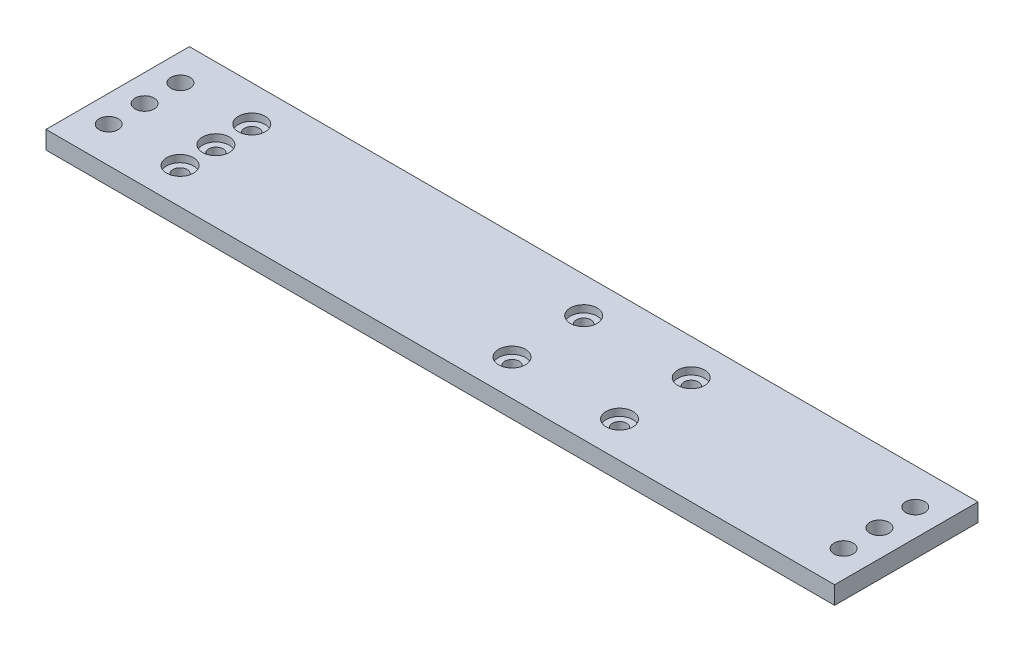
SolidWorks part; units mm, degrees
ref_plane "Front" through (0, 0, 0) normal (0, 0, 1) x (1, 0, 0)
ref_plane "Top" through (0, 0, 0) normal (0, 1, 0) x (1, 0, 0)
ref_plane "Right" through (0, 0, 0) normal (1, 0, 0) x (0, 0, -1)
sketch "Sketch1" plane through (0, 0, 0) normal (0, 1, 0) x (1, 0, 0)
  line L1 (-139.7, -25.4) -> (139.7, -25.4)
  line L2 (-139.7, -25.4) -> (-139.7, 25.4)
  line L3 (-139.7, 25.4) -> (139.7, 25.4)
  line L4 (139.7, -25.4) -> (139.7, 25.4)
  line L5 (-139.7, -25.4) -> (139.7, 25.4) construction
  line L6 (-139.7, 25.4) -> (139.7, -25.4) construction
  point P0 (0, 0)
  dimension "D1" = 50.8
  dimension "D2" = 279.4
extrude "Boss-Extrude1" add sketch "Sketch1" along normal blind 6.35
sketch "Sketch4" plane through (0, 6.35, 0) normal (0, 1, 0) x (1, 0, 0)
  line L0 (139.7, -25.4) -> (139.7, 25.4) construction
  line L1 (12.7, -12.7) -> (12.7, 12.7) construction
  line L2 (-139.7, 25.4) -> (-139.7, -25.4) construction
  line L3 (-104.902, 25.4) -> (-104.902, 12.7) construction
  line L4 (139.7, 25.4) -> (-139.7, 25.4) construction
  line L5 (-104.902, 12.7) -> (-104.902, 0) construction
  line L6 (-104.902, 0) -> (-104.902, -12.7) construction
  line L7 (-104.902, -12.7) -> (-104.902, -25.4) construction
  line L8 (-139.7, -25.4) -> (139.7, -25.4) construction
  point P0 (50.8, 12.7)
  point P2 (12.7, 12.7)
  point P4 (12.7, -12.7)
  point P6 (50.8, -12.7)
  point P23 (12.7, 0)
  point P25 (-104.902, 12.7)
  point P27 (-104.902, 0)
  point P29 (-104.902, -12.7)
  dimension "D1" = 38.1
  dimension "D2" = 88.9
  dimension "D3" = 25.4
  dimension "D4" = 34.798
hole_wizard "CBORE for #10 Socket Head Cap Screw1" positions "Sketch4" profile "Sketch3" counterbore size "#10" standard "ANSI Inch" end condition through all
sketch "Sketch3" plane through (50.8, 6.35, -12.7) normal (1, 0, 0) x (0, 0, 1)
  line L0 (0, 0) -> (0, 6.35)
  line L1 (0, 6.35) -> (2.5527, 6.35)
  line L3 (2.5527, 6.35) -> (2.5527, 2.54)
  line L4 (2.5527, 2.54) -> (4.7625, 2.54)
  line L5 (4.7625, 2.54) -> (4.7625, 0)
  line L7 (4.7625, 0) -> (0, 0)
  line L11 (0, -6.35) -> (0, 107.95) construction
  dimension "Thru Hole Dia." = 5.1054
  dimension "Thru Hole Depth" = 6.35
  dimension "C'Bore Dia." = 9.525
  dimension "C'Bore Depth" = 2.54
sketch "Sketch7" plane through (0, 0, 0) normal (0, -1, 0) x (1, 0, 0)
  line L5 (-130.175, 25.4) -> (-130.175, 12.7) construction
  line L6 (-139.7, 25.4) -> (139.7, 25.4) construction
  line L7 (-130.175, 12.7) -> (-130.175, 0) construction
  line L8 (-130.175, 0) -> (-130.175, -12.7) construction
  line L9 (-130.175, -12.7) -> (-130.175, -25.4) construction
  line L10 (139.7, -25.4) -> (-139.7, -25.4) construction
  line L12 (-139.7, -25.4) -> (-139.7, 25.4) construction
  line L13 (139.7, 25.4) -> (139.7, -25.4) construction
  point P0 (-130.175, 12.7)
  point P2 (-130.175, 0)
  point P4 (-130.175, -12.7)
  point P6 (130.175, 12.7)
  point P8 (130.175, 0)
  point P10 (130.175, -12.7)
  point P53 (0, 0)
  dimension "D1" = 9.525
  dimension "D2" = 9.525
hole_wizard "1/4 Clearance Hole1" positions "Sketch7" profile "Sketch6" hole size "1/4" standard "ANSI Inch" end condition through all
sketch "Sketch6" plane through (-130.175, 0, 12.7) normal (1, 0, 0) x (0, 0, -1)
  line L0 (0, 0) -> (0, 6.35)
  line L1 (0, 6.35) -> (3.3782, 6.35)
  line L2 (3.3782, 6.35) -> (3.3782, 0)
  line L5 (3.3782, 0) -> (0, 0)
  line L11 (0, -6.35) -> (0, 107.95) construction
  dimension "Thru Hole Dia." = 6.7564
  dimension "Thru Hole Depth" = 6.35
